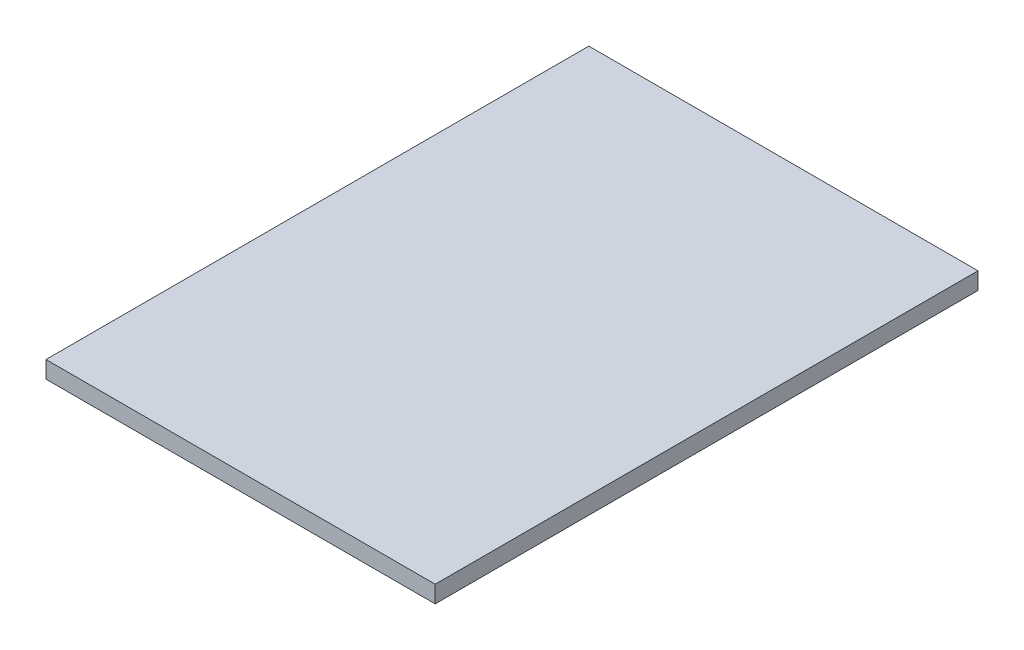
SolidWorks part; units mm, degrees
ref_plane "Front Plane" through (0, 0, 0) normal (0, 0, 1) x (1, 0, 0)
ref_plane "Top Plane" through (0, 0, 0) normal (0, 1, 0) x (1, 0, 0)
ref_plane "Right Plane" through (0, 0, 0) normal (1, 0, 0) x (0, 0, -1)
sketch "Sketch1" plane through (0, 0, 0) normal (0, 1, 0) x (1, 0, 0)
  line L1 (-28.956, -40.386) -> (28.956, -40.386)
  line L2 (-28.956, -40.386) -> (-28.956, 40.386)
  line L3 (-28.956, 40.386) -> (28.956, 40.386)
  line L4 (28.956, -40.386) -> (28.956, 40.386)
  line L5 (-28.956, -40.386) -> (28.956, 40.386) construction
  line L6 (-28.956, 40.386) -> (28.956, -40.386) construction
  point P0 (0, 0)
  dimension "D1" = 80.772
  dimension "D2" = 57.912
extrude "Boss-Extrude1" add sketch "Sketch1" along normal blind 2.54
sketch "Sketch3" plane through (0, 2.54, 0) normal (0, 1, 0) x (1, 0, 0)
  line L0 (8.636, -31.496) -> (23.876, -31.496) construction
  line L1 (8.636, -31.496) -> (8.636, 9.144) construction
  line L2 (8.636, 9.144) -> (23.876, 9.144) construction
  line L3 (28.956, -40.386) -> (28.956, 40.386) construction
  line L4 (-28.956, -40.386) -> (28.956, -40.386) construction
  circle A0 centre (8.636, -31.496) radius 0.9
  circle A1 centre (23.876, -31.496) radius 0.9
  circle A2 centre (8.636, 9.144) radius 0.9 construction
  circle A3 centre (23.876, 9.144) radius 0.9 construction
  dimension "D1" = 1.8
  dimension "D2" = 40.64
  dimension "D3" = 15.24
  dimension "D4" = 5.08
  dimension "D5" = 8.89
extrude "Boss-Extrude3" [suppressed] add sketch "Sketch3" along normal blind 12.7
sketch "Sketch4" plane through (-28.956, 0, 0) normal (-1, 0, 0) x (0, 0, 1)
  line L0 (-10.883, 2.54) -> (-10.883, 16.2343)
  line L1 (-40.386, 2.54) -> (40.386, 2.54) construction
  line L2 (-10.883, 16.2343) -> (-8.3278, 16.2343)
  line L3 (-8.3278, 16.2343) -> (-8.3278, 8.89)
  line L4 (-8.3278, 8.89) -> (10.7222, 8.89)
  line L5 (10.7222, 8.89) -> (10.7222, 16.2343)
  line L6 (10.7222, 16.2343) -> (13.2773, 16.2343)
  line L7 (13.2773, 16.2343) -> (13.2773, 2.54)
  line L9 (13.2773, 2.54) -> (-10.883, 2.54)
  dimension "D1" = 19.05
  dimension "D2" = 6.35
extrude "Boss-Extrude4" [suppressed] add sketch "Sketch4" against normal blind 12.7 from offset 5.08 offset against normal yes
